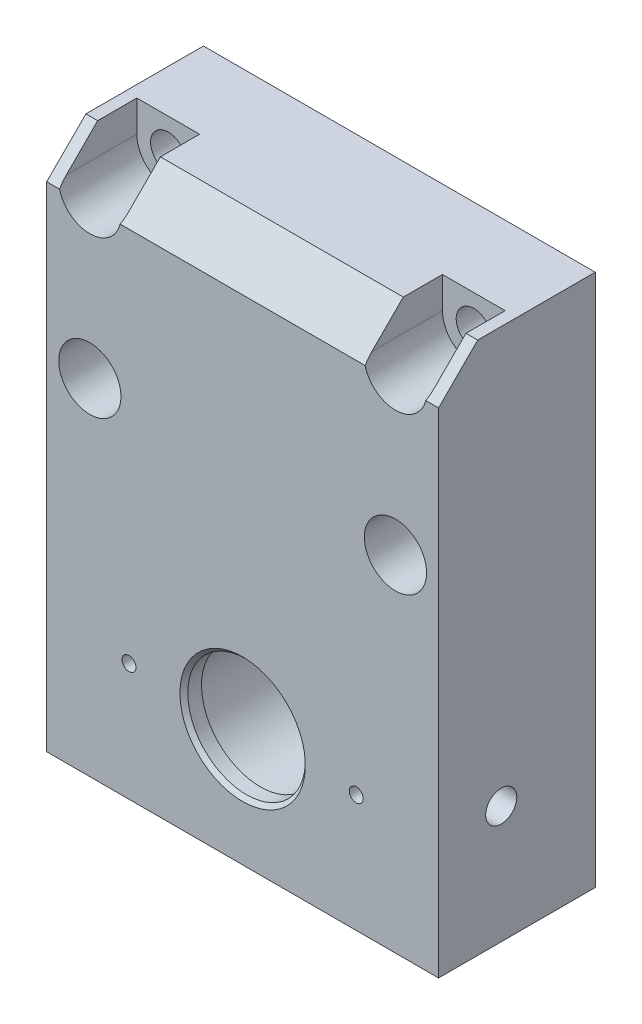
SolidWorks part; units mm, degrees
material "AISI 316 Annealed Stainless Steel Bar (SS)"
ref_plane "Front" through (0, 0, 0) normal (0, 0, 1) x (1, 0, 0)
ref_plane "Top" through (0, 0, 0) normal (0, 1, 0) x (1, 0, 0)
ref_plane "Right" through (0, 0, 0) normal (1, 0, 0) x (0, 0, -1)
sketch "Sketch1" plane through (0, 0, 0) normal (0, 0, 1) x (1, 0, 0)
  line L0 (0, 53) -> (0, 0) construction
  line L1 (-25, -15) -> (25, -15)
  line L2 (-25, -15) -> (-25, 53)
  line L3 (-25, 53) -> (25, 53)
  line L4 (25, -15) -> (25, 53)
  circle A0 centre (0, 0) radius 9.5 construction
  dimension "D3" = 19
  dimension "D5" = 15
  dimension "D1" = 68
  dimension "D2" = 50
extrude "Boss-Extrude1" add sketch "Sketch1" along normal blind 20
sketch "Sketch3" plane through (0, 0, 0) normal (1, 0, 0) x (0, 0, -1)
  line L0 (0, 0) -> (-20, 0)
  line L1 (-20, 0) -> (-20, 7.5)
  line L2 (-20, 7.5) -> (-17.75, 7.5)
  line L3 (-17.75, 7.5) -> (-17.75, 8)
  line L4 (-17.75, 8) -> (-7, 8)
  line L5 (-7, 8) -> (-7, 11)
  line L6 (-7, 11) -> (0, 11)
  line L7 (0, 53) -> (0, 0) construction
  line L8 (0, 11) -> (0, 0)
  line L9 (-20, -15) -> (-20, 53) construction
  dimension "D1" = 11
  dimension "D2" = 8
  dimension "D3" = 7.5
  dimension "D4" = 7
  dimension "D5" = 2.25
revolve "Cut-Revolve1" cut sketch "Sketch3" angle 360 about L0
hole_wizard "5/32 (0.15625) Diameter Hole1" positions "Sketch4" profile "Sketch5" hole size "5/32" standard "ANSI Inch" end condition up to next
sketch "Sketch4" plane through (25, 0, 0) normal (1, 0, 0) x (0, 0, -1)
  line L1 (0, 0) -> (-20, 0) construction
  line L2 (-20, -15) -> (-20, 53) construction
  point P0 (-12, 0)
  point P13 (-10, 0)
  point P14 (-14.4599, 0)
  dimension "D1" = 8
sketch "Sketch5" plane through (25, 0, 12) normal (0, 1, 0) x (0, 0, -1)
  line L0 (0, 0) -> (0, 17)
  line L1 (0, 17) -> (1.9844, 17)
  line L2 (1.9844, 17) -> (1.9844, 0)
  line L5 (1.9844, 0) -> (0, 0)
  line L11 (0, -6.35) -> (0, 107.95) construction
  dimension "Thru Hole Dia." = 3.9688
  dimension "Thru Hole Depth" = 17
fillet "Fillet1" radius 5 1 edges at (0, 53, 20) profile chamfer
hole_wizard "#2-56 Tapped Hole1" positions "Sketch8" profile "Sketch9" tap size "#2-56" standard "ANSI Inch"
sketch "Sketch8" plane through (0, 0, 20) normal (0, 0, 1) x (1, 0, 0)
  line L0 (-14.5, 0) -> (14.5, 0)
  point P0 (-14.5, 0)
  point P2 (14.5, 0)
  dimension "D1" = 29
sketch "Sketch9" plane through (-14.5, 0, 20) normal (1, 0, 0) x (0, -1, 0)
  line L0 (0, 0) -> (0, 8.4542)
  line L1 (0, 8.4542) -> (0.889, 7.92)
  line L2 (0.889, 7.92) -> (0.889, 0)
  line L5 (0.889, 0) -> (0, 0)
  line L10 (0, 8.4542) -> (-0.889, 7.92) construction
  line L11 (0, -6.35) -> (0, 107.95) construction
  dimension "Tap Drill Dia." = 1.778
  dimension "Tap Drill Depth" = 7.92
  dimension "Drill Angle" = 118
cosmetic thread "Hole Thread1" parameters "D1"=6.2259, "D2"=2.1844
cosmetic thread "Hole Thread2" parameters "D1"=6.555, "D2"=2.1844
sketch "Sketch19" plane through (0, 0, 20) normal (0, 0, 1) x (1, 0, 0)
  line L0 (23.5, 53) -> (23.5, 49)
  line L1 (15.5, 49) -> (15.5, 53)
  line L2 (15.5, 53) -> (23.5, 53)
  line L3 (0, 0) -> (0, 48) construction
  line L4 (25, 48) -> (-25, 48) construction
  line L6 (-25, 53) -> (25, 53) construction
  line L7 (-15.5, 53) -> (-23.5, 53)
  line L8 (-15.5, 49) -> (-15.5, 53)
  line L9 (-23.5, 53) -> (-23.5, 49)
  line L10 (25, 53) -> (25, 48) construction
  arc A0 (23.5, 49) -> (15.5, 49) centre (19.5, 49) cw
  arc A1 (-23.5, 49) -> (-15.5, 49) centre (-19.5, 49) ccw
  dimension "D3" = 4
  dimension "D1" = 5.5
  dimension "D2" = 4
extrude "Cut-Extrude2" cut sketch "Sketch19" against normal blind 10
hole_wizard "#8 Clearance Hole1" positions "Sketch20" profile "Sketch21" hole size "#8" standard "ANSI Inch" end condition through all
sketch "Sketch20" plane through (0, 0, 10) normal (0, 0, 1) x (1, 0, 0)
  point P0 (19.5, 49)
  point P5 (-19.5, 49)
sketch "Sketch21" plane through (19.5, 49, 10) normal (1, 0, 0) x (0, -1, 0)
  line L0 (0, 0) -> (0, 10)
  line L1 (0, 10) -> (2.2479, 10)
  line L2 (2.2479, 10) -> (2.2479, 0)
  line L5 (2.2479, 0) -> (0, 0)
  line L11 (0, -6.35) -> (0, 107.95) construction
  dimension "Thru Hole Dia." = 4.4958
  dimension "Thru Hole Depth" = 10
hole_wizard "CBORE for #8 Socket Head Cap Screw1" positions "Sketch16" profile "Sketch17" counterbore size "#8" standard "ANSI Inch" end condition through all
sketch "Sketch16" plane through (0, 0, 20) normal (0, 0, 1) x (1, 0, 0)
  line L0 (-19.5, 29) -> (-19.5, 49) construction
  line L1 (-19.5, 49) -> (19.5, 49) construction
  line L2 (19.5, 49) -> (19.5, 29) construction
  line L5 (0, 49) -> (0, 53) construction
  line L8 (-25, 48) -> (-25, -15) construction
  line L9 (-15.5, 53) -> (15.5, 53) construction
  point P0 (-19.5, 29)
  point P6 (19.5, 29)
  dimension "D1" = 5.5
  dimension "D2" = 4
  dimension "D3" = 20
sketch "Sketch17" plane through (-19.5, 29, 20) normal (1, 0, 0) x (0, -1, 0)
  line L0 (0, 0) -> (0, 20)
  line L1 (0, 20) -> (2.2479, 20)
  line L3 (2.2479, 20) -> (2.2479, 10)
  line L4 (2.2479, 10) -> (3.9687, 10)
  line L5 (3.9687, 10) -> (3.9687, 0)
  line L7 (3.9687, 0) -> (0, 0)
  line L11 (0, -6.35) -> (0, 107.95) construction
  dimension "Thru Hole Dia." = 4.4958
  dimension "Thru Hole Depth" = 20
  dimension "C'Bore Dia." = 7.9375
  dimension "C'Bore Depth" = 10
hole_wizard "1/8 (0.1250) Dowel Hole1" positions "Sketch10" profile "Sketch11" hole size "1/8" standard "ANSI Inch"
sketch "Sketch10" plane through (0, 0, 0) normal (0, 0, -1) x (-1, 0, 0)
  line L10 (-19.5, 49) -> (-19.5, 29) construction
  point P0 (-19.5, 39)
  point P24 (0, 0)
  point P25 (-19.5, 39)
sketch "Sketch11" plane through (19.5, 39, 0) normal (1, 0, 0) x (0, 1, 0)
  line L0 (0, 0) -> (0, 5.9539)
  line L1 (0, 5.9539) -> (1.5875, 5)
  line L2 (1.5875, 5) -> (1.5875, 0)
  line L5 (1.5875, 0) -> (0, 0)
  line L10 (0, 5.9539) -> (-1.5875, 5) construction
  line L11 (0, -6.35) -> (0, 107.95) construction
  dimension "Hole Dia." = 3.175
  dimension "Hole Depth" = 5
  dimension "Drill Angle" = 118
hole_wizard "1/8 (0.1250) Dowel Slot1" positions "Sketch12" profile "Sketch13" size "1/8" standard "ANSI Inch" slot yes
sketch "Sketch12" plane through (0, 0, 0) normal (0, 0, -1) x (-1, 0, 0)
  line L0 (17.5, 39) -> (21.5, 39) construction
  line L5 (19.5, 29) -> (19.5, 49) construction
  point P0 (19.5, 39)
  point P16 (0, 0)
  point P17 (19.5, 39)
  point P20 (0, 0)
  dimension "D1" = 4
sketch "Sketch13" plane through (-19.5, 39, 0) normal (1, 0, 0) x (0, 1, 0)
  line L0 (0, 0) -> (0, 5.9539)
  line L1 (0, 5.9539) -> (1.5875, 5)
  line L2 (1.5875, 5) -> (1.5875, 0)
  line L5 (1.5875, 0) -> (0, 0)
  line L10 (0, 5.9539) -> (-1.5875, 5) construction
  line L11 (0, -6.35) -> (0, 107.95) construction
  dimension "Hole Dia." = 3.175
  dimension "Hole Depth" = 5
  dimension "Drill Angle" = 118
sketch "Sketch22" plane through (0, 0, 0) normal (0, 0, -1) x (-1, 0, 0)
  circle A0 centre (0, 0) radius 10
  dimension "D1" = 20
extrude "Cut-Extrude3" [suppressed] cut sketch "Sketch22" along normal blind 1.1 from offset 2 offset against normal yes
chamfer "Chamfer1" distance 0.5 angle 45 2 edges at (0, 11, 0) (0, 7.5, 20)
